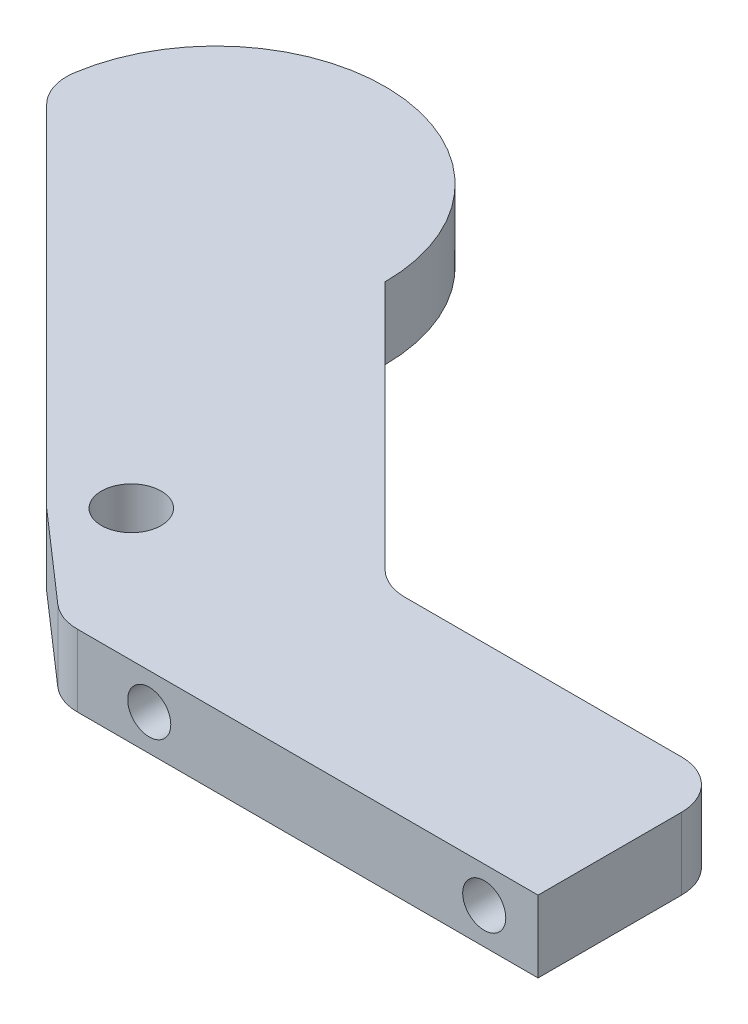
SolidWorks part; units mm, degrees
ref_plane "Front Plane" through (0, 0, 0) normal (0, 0, 1) x (1, 0, 0)
ref_plane "Top Plane" through (0, 0, 0) normal (0, 1, 0) x (1, 0, 0)
ref_plane "Right Plane" through (0, 0, 0) normal (1, 0, 0) x (0, 0, -1)
sketch "Sketch1" plane through (0, 0, 0) normal (0, 1, 0) x (1, 0, 0)
  line L0 (0, 6.35) -> (12.3665, 6.35)
  line L1 (12.3665, 6.35) -> (57.15, 6.35)
  line L2 (6.35, 0) -> (6.35, -13.97)
  line L3 (6.35, -13.97) -> (57.15, -13.97)
  line L4 (57.15, 6.35) -> (57.15, -13.97)
  line L5 (20.5908, 6.35) -> (-7.3492, 34.29)
  line L6 (-4.4901, -4.4901) -> (-43.2703, 34.29)
  line L7 (-4.4901, -4.4901) -> (6.35, -13.97)
  circle A0 centre (0, 0) radius 3.175
  arc A1 (0, 6.35) -> (6.35, 0) centre (0, 0) ccw
  arc A2 (-43.2703, 34.29) -> (-7.3492, 34.29) centre (-25.3097, 34.29) cw
  dimension "D1" = 12.7
  dimension "D2" = 6.35
  dimension "D3" = 6.35
  dimension "D4" = 50.8
  dimension "D5" = 20.32
  dimension "D6" = 45
  dimension "D7" = 25.4
  dimension "D8" = 27.94
extrude "Boss-Extrude1" add sketch "Sketch1" along normal mid plane 7.62 contours A2 L6 A1 L0 L1 L5 | L0 A1 L2 L3 L4 L1 A0 | A1 L7 L2 region at (-15.7867, 0, -26.7963) region at (28.8904, 0, 3.4247) region at (3.6646, 0, 8.0416)
sketch "Sketch2" plane through (0, 0, 13.97) normal (0, 0, 1) x (1, 0, 0)
  circle A0 centre (51.4379, 0) radius 1.8987 construction
  circle A1 centre (15.8779, 0) radius 1.8987 construction
  circle A2 centre (51.4379, 0) radius 1.8986
  circle A3 centre (15.8779, 0) radius 1.8987
  circle A4 centre (15.8779, 0) radius 2.286
  circle A5 centre (51.4379, 0) radius 2.286
  dimension "D1" = 4.572
  dimension "D2" = 4.572
extrude "Cut-Extrude1" cut sketch "Sketch2" against normal blind 5.08 contours A4 | A5 | A3 | A2 region at (51.4379, 0, 13.97) region at (15.8779, 0, 13.97) region at (13.6566, 0, 13.97) region at (49.2166, 0, 13.97)
fillet "Fillet1" radius 5.08 4 edges at (57.15, 0, -6.35) (20.5908, 0, -6.35) (6.35, 0, 13.97) (-43.2703, 0, -34.29)
